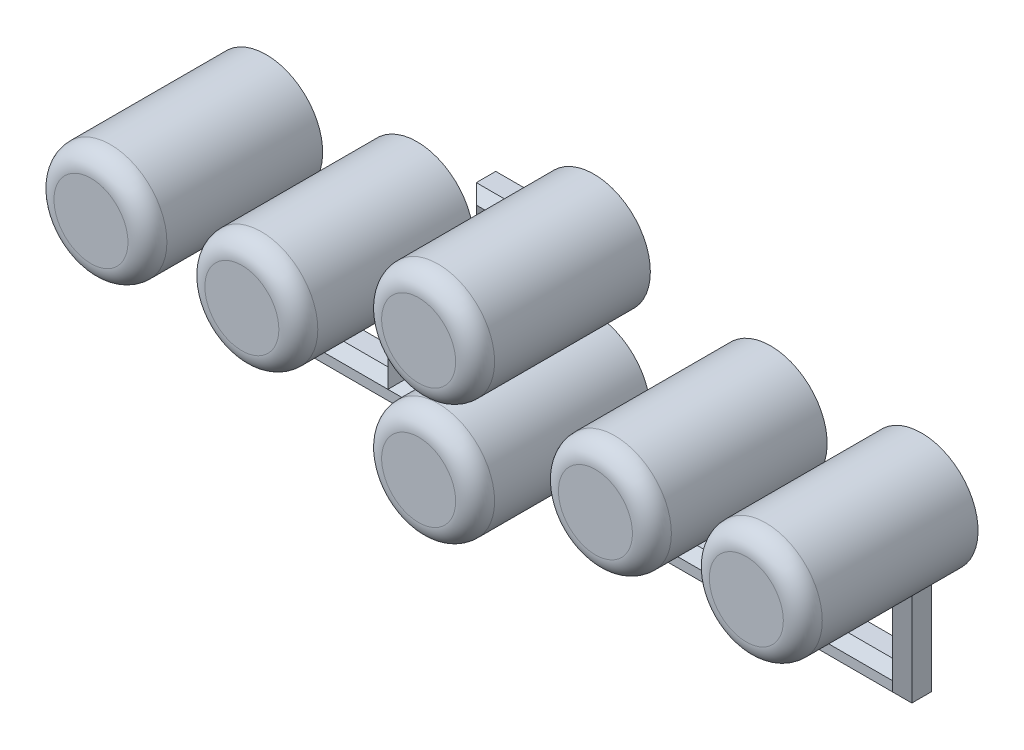
SolidWorks part; units mm, degrees
ref_plane "Спереди" through (0, 0, 0) normal (0, 0, 1) x (1, 0, 0)
ref_plane "Сверху" through (0, 0, 0) normal (0, 1, 0) x (1, 0, 0)
ref_plane "Справа" through (0, 0, 0) normal (1, 0, 0) x (0, 0, -1)
sketch "Эскиз1" plane through (0, 0, 0) normal (0, 0, 1) x (1, 0, 0)
  line L0 (0, 0) -> (7.75, 0)
  line L1 (7.75, 0) -> (25.91, 0)
  line L2 (25.91, 0) -> (33.66, 0)
  line L3 (16.83, 0) -> (16.83, -3.1)
  circle A0 centre (0, 0) radius 2.9
  circle A1 centre (7.75, 0) radius 2.9
  circle A2 centre (25.91, 0) radius 2.9
  circle A3 centre (33.66, 0) radius 2.9
  circle A4 centre (16.83, -3.1) radius 2.9
  circle A5 centre (16.83, 3.1) radius 2.9
  dimension "D5" = 5.8
  dimension "D1" = 7.75
  dimension "D2" = 18.16
  dimension "D3" = 7.75
  dimension "D4" = 3.1
extrude "Бобышка-Вытянуть1" add sketch "Эскиз1" along normal blind 9 contours L1 A1 L0 | L0 A1 L1 | A0 | A5 | A4 | L2 A2 L1 | A3 | L1 A2 L2 region at (33.66, 2.818, 0) region at (25.91, 1.2308, 0) region at (25.91, -1.2308, 0) region at (18.8226, -1.1074, 0) region at (7.75, 1.2308, 0) region at (7.75, -1.2308, 0) region at (-2.818, 0, 0) region at (16.83, 3.1, 0)
sketch "Эскиз2" plane through (0, 0, 0) normal (0, 0, -1) x (-1, 0, 0)
  line L12 (0, 0) -> (0.5, 0)
  line L13 (0.5, 0) -> (0.5, -8.3652)
  line L14 (0.5, -8.3652) -> (-34.16, -8.3652)
  line L15 (-34.16, -8.3652) -> (-34.16, 0)
  line L16 (-34.16, 0) -> (-33.66, 0)
  line L17 (-33.16, 0) -> (-33.16, -6.8652)
  line L18 (-33.16, -6.8652) -> (-26.41, -6.8652)
  line L19 (-26.41, -6.8652) -> (-26.41, 0)
  line L20 (-26.41, 0) -> (-25.41, 0)
  line L21 (-25.41, 0) -> (-25.41, -6.8652)
  line L22 (-25.41, -6.8652) -> (-21.87, -6.8652)
  line L23 (-21.87, -6.8652) -> (-21.87, -2.6)
  line L24 (-21.87, -2.6) -> (-16.83, -2.6)
  line L25 (-16.83, -2.6) -> (-16.83, -3.1)
  line L26 (-16.83, -3.1) -> (-16.83, -3.6)
  line L27 (-16.83, -3.6) -> (-20.87, -3.6)
  line L28 (-20.87, -3.6) -> (-20.87, -6.8652)
  line L29 (-20.87, -6.8652) -> (-12.79, -6.8652)
  line L30 (-12.79, -6.8652) -> (-12.79, 2.6)
  line L31 (-12.79, 2.6) -> (-16.83, 2.6)
  line L32 (-16.83, 2.6) -> (-16.83, 3.1)
  line L33 (-16.83, 3.6) -> (-11.79, 3.6)
  line L34 (-11.79, 3.6) -> (-11.79, -6.8652)
  line L35 (-11.79, -6.8652) -> (-8.25, -6.8652)
  line L36 (-8.25, -6.8652) -> (-8.25, 0)
  line L37 (-8.25, 0) -> (-7.75, 0)
  line L38 (-7.25, 0) -> (-7.25, -6.8652)
  line L39 (-7.25, -6.8652) -> (-0.5, -6.8652)
  line L40 (-0.5, -6.8652) -> (-0.5, 0)
  line L41 (-0.5, 0) -> (0, 0)
  line L42 (-16.83, 3.1) -> (-16.83, 3.6)
  line L43 (-7.75, 0) -> (-7.25, 0)
  line L44 (-33.66, 0) -> (-33.16, 0)
  dimension "D1" = 0.5
  dimension "D2" = 0.5
  dimension "D19" = 0.5
  dimension "D20" = 0.5
  dimension "D21" = 0.5
  dimension "D22" = 0.5
extrude "Бобышка-Вытянуть2" add sketch "Эскиз2" against normal blind 1.5
chamfer "Фаска1" distance 0.5 angle 45 11 edges at (12.79, -2.1326, 1.5) (16.83, -6.8652, 1.5) (20.87, -5.2326, 1.5) (20.7783, -2.6, 1.5) (21.87, -4.7326, 1.5) (25.41, -4.8609, 1.5) (26.41, -4.8609, 1.5) (29.785, -6.8652, 1.5) (33.16, -4.8609, 1.5) (16.83, -8.3652, 1.5) (34.16, -5.6109, 1.5)
chamfer "Фаска2" distance 0.5 angle 45 1 edges at (13.1317, 2.6, 1.5)
chamfer "Фаска3" distance 0.5 angle 45 8 edges at (-0.5, -5.3609, 1.5) (0.5, -4.8609, 1.5) (3.875, -6.8652, 1.5) (7.25, -4.8609, 1.5) (8.25, -4.8609, 1.5) (10.02, -6.8652, 1.5) (11.79, -1.6326, 1.5) (12.8817, 3.6, 1.5)
chamfer "Фаска4" distance 0.5 angle 45 1 edges at (23.64, -6.8652, 1.5)
fillet "Скругление2" radius 1 6 edges at (2.9, 0, 9) (10.65, 0, 9) (19.73, 3.1, 9) (19.73, -3.1, 9) (28.81, 0, 9) (36.56, 0, 9)
